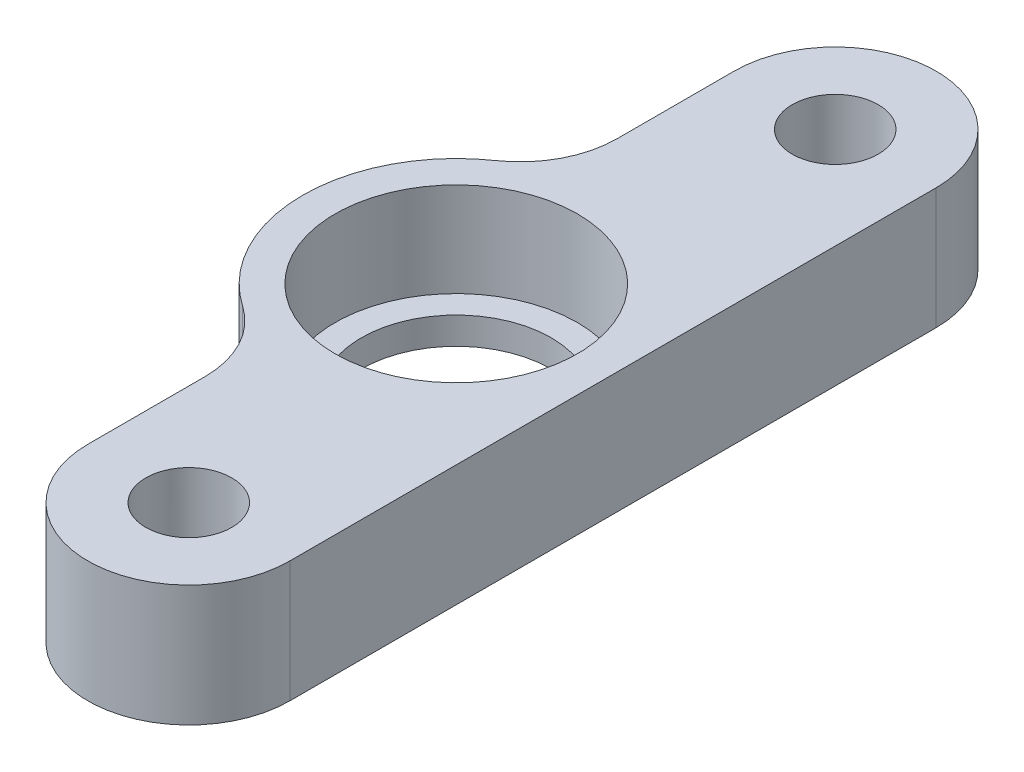
SolidWorks part; units mm, degrees
ref_plane "Front Plane" through (0, 0, 0) normal (0, 0, 1) x (1, 0, 0)
ref_plane "Top Plane" through (0, 0, 0) normal (0, 1, 0) x (1, 0, 0)
ref_plane "Right Plane" through (0, 0, 0) normal (1, 0, 0) x (0, 0, -1)
sketch "Sketch1" plane through (0, 0, 0) normal (0, 1, 0) x (1, 0, 0)
  line L0 (0, -50.8) -> (0, 50.8) construction
  line L1 (-3.556, 11.5291) -> (-3.556, 25.4)
  line L2 (-3.556, -11.5291) -> (-3.556, -25.4)
  line L4 (12.319, 25.4) -> (12.319, -25.4)
  circle A5 centre (0, 0) radius 9.525
  arc A6 (-3.556, 11.5291) -> (-3.556, -11.5291) centre (0, 0) ccw
  arc A7 (12.319, -25.4) -> (-3.556, -25.4) centre (4.3815, -25.4) cw
  arc A8 (12.319, 25.4) -> (-3.556, 25.4) centre (4.3815, 25.4) ccw
  point P7 (0, 0)
  point P14 (0, 0)
  dimension "D1" = 2.54
  dimension "D6" = 50.8
  dimension ".750" = 19.05
  dimension "D2" = 7.9375
  dimension "D4" = 4.3815
  dimension "D3" = 101.6
extrude "Boss-Extrude1" add sketch "Sketch1" along normal mid plane 9.525 contours L0 L4 A5 | L0 A5 L1 A6 L2 region at (-2.8461, 0, -18.4645)
sketch "Sketch2" plane through (0, -4.7625, 0) normal (0, 1, 0) x (1, 0, 0)
  point P30 (4.3815, -25.4)
  point P33 (4.3815, 25.4)
hole_wizard "CSK for 1/4 Flat Head Machine Screw1" positions "Sketch2" profile "Sketch3" countersink size "1/4" standard "ANSI Inch" end condition up to next
sketch "Sketch3" plane through (4.3815, -4.7625, 25.4) normal (1, 0, 0) x (0, 0, -1)
  line L0 (0, 0) -> (0, 9.525)
  line L1 (0, 9.525) -> (3.3782, 9.525)
  line L2 (3.3782, 9.525) -> (3.3782, 3.7749)
  line L3 (3.3782, 3.7749) -> (6.6597, 0)
  line L5 (6.6597, 0) -> (0, 0)
  line L6 (-3.3782, 3.7749) -> (-6.6597, 0) construction
  line L11 (0, -6.35) -> (0, 107.95) construction
  dimension "Thru Hole Dia." = 6.7564
  dimension "Thru Hole Depth" = 9.525
  dimension "Near C'Sink Dia." = 13.3194
  dimension "Near C'Sink Angle" = 82
fillet "Fillet1" radius 7.62 2 edges at (-3.556, 0, 11.5291) (-3.556, 0, -11.5291)
sketch "Sketch4" plane through (0, -4.7625, 0) normal (0, -1, 0) x (1, 0, 0)
  circle A0 centre (0, 0) radius 7.4612
  circle A1 centre (0, 0) radius 9.525
  circle A2 centre (0, 0) radius 9.525 construction
  dimension "D1" = 14.9225
extrude "Boss-Extrude2" add sketch "Sketch4" against normal blind 2.1273
